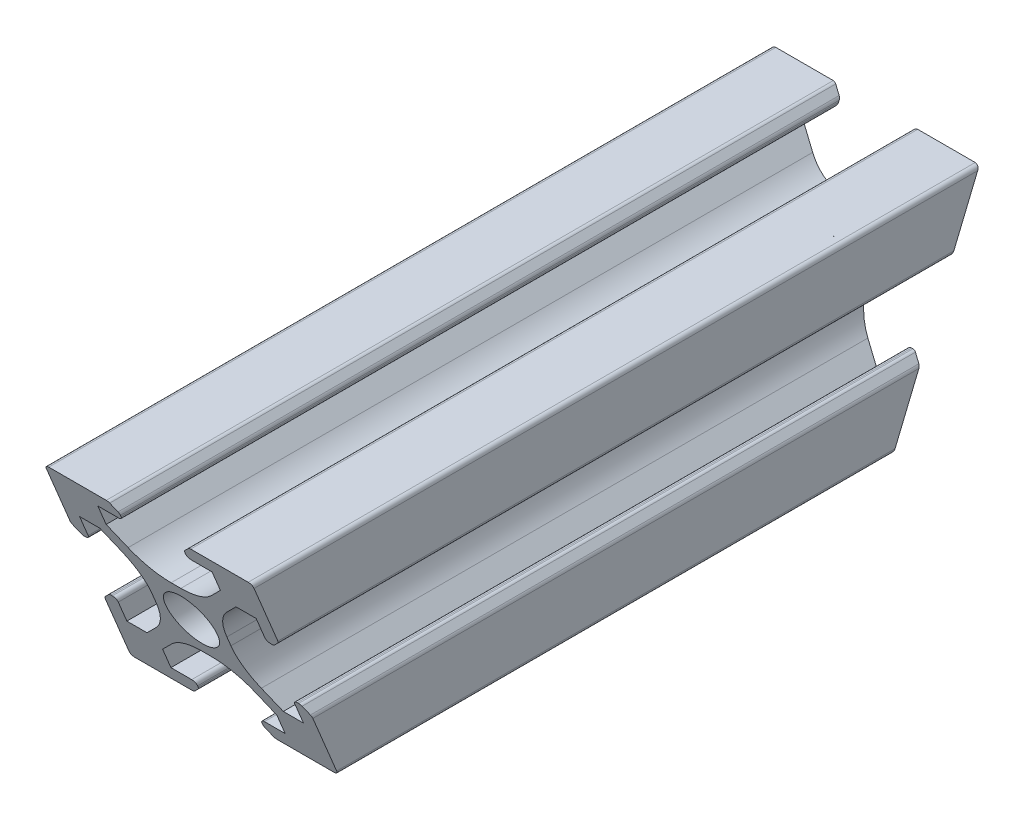
SolidWorks part; units mm, degrees
material "6063-O"
ref_plane "Plano frontal" through (0, 0, 0) normal (0, 0, 1) x (1, 0, 0)
ref_plane "Plano superior" through (0, 0, 0) normal (0, 1, 0) x (1, 0, 0)
ref_plane "Plano direito" through (0, 0, 0) normal (1, 0, 0) x (0, 0, -1)
sketch "Esboço1" plane through (0, 0, 0) normal (0, 0, 1) x (1, 0, 0)
  line L0 (-9.0343, 3.1) -> (-8.9, 3.1)
  line L3 (-10, 10) -> (-4.0657, 10)
  line L5 (-10, -10) -> (10, 10) construction
  line L6 (-10, 10) -> (10, -10) construction
  line L7 (-8.5, 3.5) -> (-8.5, 5.5)
  line L8 (-10, 0) -> (10, 0) construction
  line L9 (0, 10) -> (0, -10) construction
  line L12 (-8.5, 5.5) -> (-6.5607, 5.5)
  line L15 (-6.5607, 5.5) -> (-5.0645, 4.0038)
  line L16 (-3.6, 0.4683) -> (-3.6, 0)
  line L17 (-0.4683, 3.6) -> (0, 3.6)
  line L18 (-5.5, 6.5607) -> (-4.0038, 5.0645)
  line L21 (-5.5, 8.5) -> (-5.5, 6.5607)
  line L24 (-3.5, 8.5) -> (-5.5, 8.5)
  line L25 (-3.1, 9.0343) -> (-3.1, 8.9)
  line L44 (-10, 4.0657) -> (-10, 10)
  line L45 (-9.8828, 3.7828) -> (-9.3172, 3.2172)
  line L46 (-3.7828, 9.8828) -> (-3.2172, 9.3172)
  line L47 (-3.6, 0) -> (-2.5, 0)
  line L48 (0, 3.6) -> (0, 2.5)
  arc A0 (-3.5, 8.5) -> (-3.1, 8.9) centre (-3.5, 8.9) ccw
  arc A1 (-3.7828, 9.8828) -> (-4.0657, 10) centre (-4.0657, 9.6) ccw
  arc A2 (-10, 4.0657) -> (-9.8828, 3.7828) centre (-9.6, 4.0657) ccw
  arc A3 (-8.5, 3.5) -> (-8.9, 3.1) centre (-8.9, 3.5) cw
  arc A4 (-3.2172, 9.3172) -> (-3.1, 9.0343) centre (-3.5, 9.0343) cw
  arc A5 (-9.3172, 3.2172) -> (-9.0343, 3.1) centre (-9.0343, 3.5) ccw
  arc A6 (-3.6, 0.4683) -> (-5.0645, 4.0038) centre (-8.6, 0.4683) ccw
  arc A7 (-4.0038, 5.0645) -> (-0.4683, 3.6) centre (-0.4683, 8.6) ccw
  circle A8 centre (0, 0) radius 2.5
  point P6 (-10, 3.1)
  point P28 (-3.1, 8.5)
  point P31 (-3.1, 10)
  point P33 (-3.9, 10)
  point P36 (-10, 3.9)
  point P39 (-8.5, 3.1)
  point P42 (-3.1, 9.2)
  point P45 (-9.2, 3.1)
  point P48 (-3.6, 2.5393)
  point P51 (-2.5393, 3.6)
  dimension "D5" = 10
  dimension "D9" = 0.4
  dimension "D10" = 0.4
  dimension "D11" = 5
  dimension "D12" = 5
  dimension "D13" = 5
  dimension "D1" = 6.9
  dimension "D2" = 1.5
  dimension "D3" = 3.6
  dimension "D4" = 1.5
  dimension "D6" = 2.4
  dimension "D7" = 3.6
  dimension "D8" = 45
extrude "Ressalto-extrusão1" add sketch "Esboço1" along normal blind 70 contours A4 A3 L3 A0 L17 L18 L21 L24 L25 L0 L7 L12 L15 L16 region at (-5.9987, 5.9987, 0)
sketch "Esboço3" plane through (0, 0, 0) normal (1, 0, 0) x (0, 0, -1)
  line L0 (0, 0) -> (-70, 0) construction
  line L1 (-70, 2.5) -> (-70, 0) construction
pattern_circular "PadrãoCircular1" count 4 every 90 about axis through (0, 0, 0) along (0, 0, 1) of "Ressalto-extrusão1"
fillet "Filete1" radius 0.4 4 edges at (-10, -10, 35) (-10, 10, 35) (10, -10, 35) (10, 10, 35)
ref_plane "Plane1" through (0, 0, 35) normal (0, 0, 1) x (1, 0, 0)
sketch "Sketch1" plane through (-10, 0, 0) normal (-1, 0, 0) x (0, 0, 1)
  line L0 (0, 10) -> (0, -10)
  line L1 (0, 0) -> (70, 0) construction
  line L2 (0, 10) -> (8.2843, -10)
  line L3 (0, -10) -> (8.2843, -10)
  line L4 (35, 9.6) -> (35, -9.6) construction
  line L5 (70, 9.6) -> (0, 9.6) construction
  line L6 (0, -9.6) -> (70, -9.6) construction
  line L7 (70, 9.6) -> (70, -9.6)
  line L8 (70, -10) -> (61.7157, -10)
  line L9 (70, 10) -> (61.7157, -10)
  line L10 (70, 10) -> (70, -10)
  line M5 (70, 4.0657) -> (70, 9.6)
  line M6 (70, 9.6) -> (0, 9.6)
  line M7 (0, 9.6) -> (0, 4.0657)
  line M8 (0, 4.0657) -> (70, 4.0657)
  dimension "D1" = 10
  dimension "D2" = 22.5
extrude "Cut-Extrude1" cut sketch "Sketch1" against normal through all contours L0 L3 L2 M8 | L2 M6 M7 M8 | L9 M6 M8 M5 | L10 L7 L9 L8 M8 | L10 L9 M6 | L2 L0 M6 region at (-10, 9.7333, 0.0552) region at (-10, 6.027, 0.8228) region at (-10, -4.2386, 2.9489) region at (-10, 6.027, 69.1772) region at (-10, 9.7333, 69.9448) region at (-10, -4.2386, 67.0511)
sketch "Sketch2" plane through (-10, 0, 0) normal (-1, 0, 0) x (0, 0, 1)
  line L0 (35, -9.6) -> (35, 9.6) construction
  line L1 (8.1186, -9.6) -> (61.8814, -9.6) construction
  line L2 (69.8343, 9.6) -> (0.1657, 9.6) construction
  line L3 (0, 0) -> (80.4315, 0) construction
  circle A0 centre (18, 0) radius 1.5
  circle A1 centre (11, 0) radius 1.5
  circle A2 centre (52, 0) radius 1.5
  circle A3 centre (59, 0) radius 1.5
  dimension "D1" = 7
  dimension "D3" = 3
  dimension "D4" = 3
  dimension "D2" = 11
extrude "Cut-Extrude2" cut sketch "Sketch2" against normal through all
